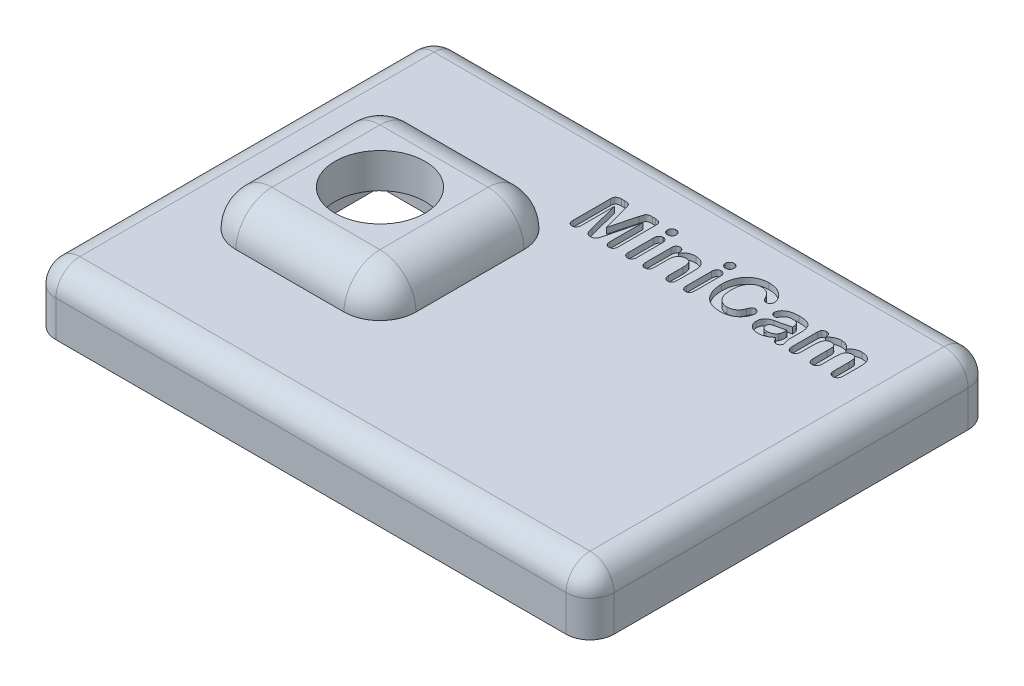
SolidWorks part; units mm, degrees
ref_plane "Front Plane" through (0, 0, 0) normal (0, 0, 1) x (1, 0, 0)
ref_plane "Top Plane" through (0, 0, 0) normal (0, 1, 0) x (1, 0, 0)
ref_plane "Right Plane" through (0, 0, 0) normal (1, 0, 0) x (0, 0, -1)
sketch "Sketch1" plane through (0, 0, 0) normal (0, 1, 0) x (1, 0, 0)
  line L1 (0, 0) -> (-46.5, 0)
  line L2 (0, 0) -> (0, 33.5)
  line L3 (0, 33.5) -> (-46.5, 33.5)
  line L4 (-46.5, 0) -> (-46.5, 33.5)
  dimension "D1" = 46.5
  dimension "D2" = 33.5
extrude "Boss-Extrude2" add sketch "Sketch1" along normal blind 2
sketch "Sketch2" plane through (0, 2, 0) normal (0, 1, 0) x (1, 0, 0)
  line L5 (-41.5, 24) -> (-26.5, 24)
  line L6 (-41.5, 24) -> (-41.5, 9)
  line L7 (-41.5, 9) -> (-26.5, 9)
  line L8 (-26.5, 24) -> (-26.5, 9)
  line L9 (-41.5, 24) -> (-26.5, 9) construction
  line L10 (-41.5, 9) -> (-26.5, 24) construction
  point P4 (-34, 16.5)
  point P12 (-34, 19.0099)
  dimension "D1" = 34
  dimension "D2" = 16.5
  dimension "D3" = 15
  dimension "D4" = 15
extrude "Boss-Extrude3" add sketch "Sketch2" along normal blind 3
sketch "Sketch3" plane through (0, 0, 0) normal (0, -1, 0) x (-1, 0, 0)
  line L0 (45.5, 1) -> (45.5, 32.5)
  line L1 (46.5, 0) -> (0, 0)
  line L2 (46.5, 0) -> (46.5, 33.5)
  line L3 (46.5, 33.5) -> (0, 33.5)
  line L4 (0, 0) -> (0, 33.5)
  line L5 (45.5, 32.5) -> (1, 32.5)
  line L6 (1, 1) -> (1, 32.5)
  line L7 (45.5, 1) -> (1, 1)
  dimension "D1" = 1
extrude "Boss-Extrude4" add sketch "Sketch3" along normal blind 3
sketch "Sketch4" plane through (0, -3, 0) normal (0, -1, 0) x (-1, 0, 0)
  line L1 (48.2558, 9.5) -> (43.2448, 9.5)
  line L2 (48.2558, 9.5) -> (48.2558, 22.5)
  line L3 (48.2558, 22.5) -> (43.2448, 22.5)
  line L4 (43.2448, 9.5) -> (43.2448, 22.5)
  dimension "D1" = 13
  dimension "D2" = 22.5
extrude "Cut-Extrude1" cut sketch "Sketch4" against normal blind 3
sketch "Sketch5" plane through (0, 0, 0) normal (0, -1, 0) x (-1, 0, 0)
  line L1 (0, 0) -> (4.9, 0)
  line L2 (0, 0) -> (0, 4.9)
  line L3 (0, 4.9) -> (4.9, 4.9)
  line L4 (4.9, 0) -> (4.9, 4.9)
  line L5 (0, 33.5) -> (4.9, 33.5)
  line L6 (0, 33.5) -> (0, 28.6)
  line L7 (0, 28.6) -> (4.9, 28.6)
  line L8 (4.9, 33.5) -> (4.9, 28.6)
  line L9 (46.5, 33.5) -> (41.6, 33.5)
  line L10 (46.5, 33.5) -> (46.5, 28.6)
  line L11 (46.5, 28.6) -> (41.6, 28.6)
  line L12 (41.6, 33.5) -> (41.6, 28.6)
  line L13 (46.5, 0) -> (41.6, 0)
  line L14 (46.5, 0) -> (46.5, 4.9)
  line L15 (46.5, 4.9) -> (41.6, 4.9)
  line L16 (41.6, 0) -> (41.6, 4.9)
  dimension "D1" = 4.9
  dimension "D2" = 4.9
  dimension "D3" = 4.9
  dimension "D4" = 4.9
  dimension "D5" = 4.9
  dimension "D6" = 4.9
  dimension "D7" = 4.9
  dimension "D8" = 4.9
extrude "Boss-Extrude5" add sketch "Sketch5" along normal blind 3
fillet "Fillet2" radius 2 8 edges at (0, 2, -16.75) (-23.25, 2, 0) (-23.25, 2, -33.5) (-46.5, 2, -16.75) (-46.5, -0.5, -33.5) (0, -0.5, -33.5) (0, -0.5, 0) (-46.5, -0.5, 0)
sketch "Sketch6" plane through (0, 5, 0) normal (0, 1, 0) x (1, 0, 0)
  circle A0 centre (-34, 16.5) radius 3.75
  dimension "D3" = 7.5
  dimension "D1" = 34
  dimension "D2" = 16.5
extrude "Cut-Extrude2" cut sketch "Sketch6" against normal blind 13
fillet "Fillet3" radius 3 4 edges at (-34, 5, -24) (-26.5, 5, -16.5) (-34, 5, -9) (-41.5, 5, -16.5)
sketch "Sketch7" plane through (0, 0, 0) normal (0, -1, 0) x (-1, 0, 0)
  line L1 (39, 21.5) -> (29, 21.5)
  line L2 (39, 21.5) -> (39, 11.5)
  line L3 (39, 11.5) -> (29, 11.5)
  line L4 (29, 21.5) -> (29, 11.5)
  line L5 (39, 21.5) -> (29, 11.5) construction
  line L6 (39, 11.5) -> (29, 21.5) construction
  point P0 (34, 16.5)
  dimension "D1" = 10
  dimension "D2" = 10
extrude "Cut-Extrude3" cut sketch "Sketch7" against normal blind 2.1
sketch "Sketch8" plane through (0, 2, 0) normal (0, 1, 0) x (1, 0, 0)
  text T0 "MiniCam" font "Arial Rounded MT Bold" height in points 16
extrude "Cut-Extrude4" cut sketch "Sketch8" against normal blind 0.5
